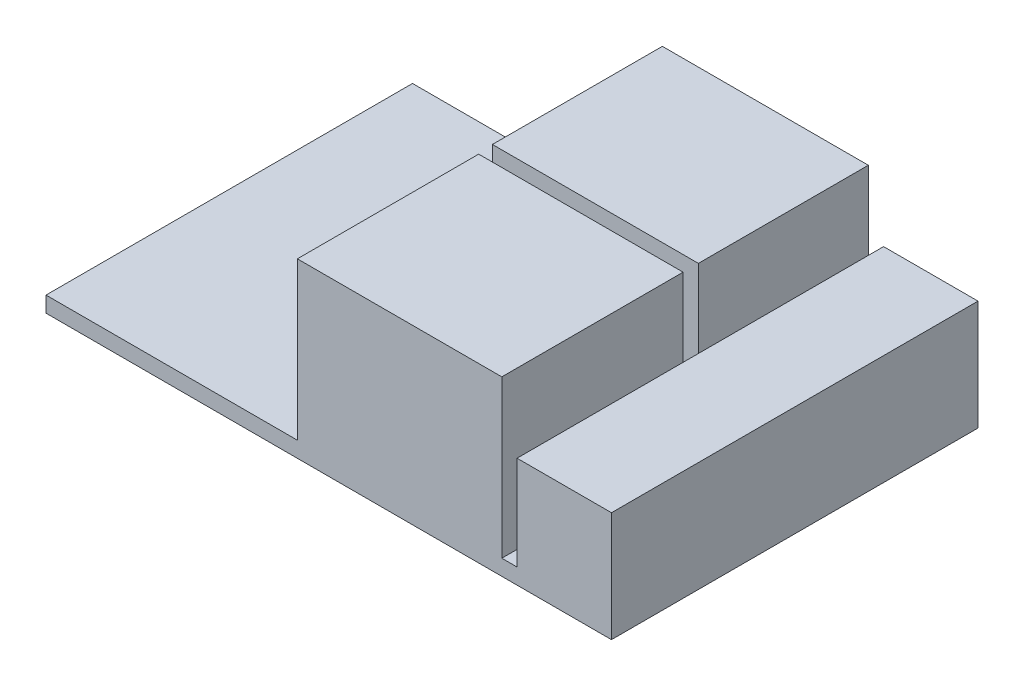
SolidWorks part; units mm, degrees
ref_plane "前视基准面" through (0, 0, 0) normal (0, 0, 1) x (1, 0, 0)
ref_plane "上视基准面" through (0, 0, 0) normal (0, 1, 0) x (1, 0, 0)
ref_plane "右视基准面" through (0, 0, 0) normal (1, 0, 0) x (0, 0, -1)
other "Configuration Table"
sketch "草图1" plane through (0, 0, 0) normal (0, 1, 0) x (1, 0, 0)
  line L0 (203.5758, 850.9118) -> (1017.879, 850.9118) construction
  line L3 (0, 137.1079) -> (54, 137.1079)
  line L4 (0, 137.1079) -> (0, 102.1079)
  line L5 (0, 102.1079) -> (54, 102.1079)
  line L6 (54, 137.1079) -> (54, 102.1079)
  line L7 (54, 137.1079) -> (47.2787, 137.1079)
  line L8 (54, 137.1079) -> (54, 102.1079)
  line L9 (54, 102.1079) -> (47.2787, 102.1079)
  line L10 (47.2787, 137.1079) -> (47.2787, 102.1079) construction
  line L11 (54, 137.1079) -> (47.2787, 102.1079) construction
  line L12 (54, 102.1079) -> (47.2787, 137.1079) construction
  line L13 (23.802, 137.1079) -> (45.2592, 137.1079)
  line L14 (23.802, 137.1079) -> (23.802, 119.6079) construction
  line L15 (23.802, 119.6079) -> (45.2592, 119.6079) construction
  line L16 (45.2592, 137.1079) -> (45.2592, 119.6079) construction
  line L17 (23.802, 137.1079) -> (45.2592, 119.6079) construction
  line L18 (23.802, 119.6079) -> (45.2592, 137.1079) construction
  line L19 (23.802, 118.4725) -> (45.2592, 118.4725) construction
  line L20 (23.802, 118.4725) -> (23.802, 102.1079) construction
  line L21 (23.802, 102.1079) -> (45.2592, 102.1079)
  line L22 (45.2592, 118.4725) -> (45.2592, 102.1079) construction
  line L23 (23.802, 118.4725) -> (45.2592, 102.1079) construction
  line L24 (23.802, 102.1079) -> (45.2592, 118.4725) construction
  point P9 (50.6394, 119.6079)
  point P14 (34.5306, 128.3579)
  point P19 (34.5306, 110.2902)
  dimension "D1" = 35
  dimension "D2" = 54
  dimension "D3" = 0
extrude "凸台-拉伸1" add sketch "草图1" along normal blind 1.5 contours L6 L3 L4 L5 region at (27, 0, -119.6079)
sketch "草图2" plane through (0, 1.5, 0) normal (0, 1, 0) x (1, 0, 0)
  line L0 (0, 102.1079) -> (54, 102.1079) construction
  line L1 (54, 137.1079) -> (44.9839, 137.1079)
  line L2 (54, 137.1079) -> (54, 102.1079)
  line L3 (54, 102.1079) -> (44.9839, 102.1079)
  line L4 (44.9839, 137.1079) -> (44.9839, 102.1079)
  line L5 (54, 137.1079) -> (44.9839, 102.1079) construction
  line L6 (54, 102.1079) -> (44.9839, 137.1079) construction
  line L7 (0, 137.1079) -> (54, 137.1079) construction
  line L8 (23.8587, 137.1079) -> (43.527, 137.1079)
  line L9 (23.8587, 137.1079) -> (23.8587, 120.8778)
  line L10 (23.8587, 120.8778) -> (43.527, 120.8778)
  line L11 (43.527, 137.1079) -> (43.527, 120.8778)
  line L12 (23.8587, 137.1079) -> (43.527, 120.8778) construction
  line L13 (23.8587, 120.8778) -> (43.527, 137.1079) construction
  line L15 (24.0044, 119.4209) -> (43.527, 119.4209)
  line L16 (24.0044, 119.4209) -> (24.0044, 102.1079)
  line L17 (24.0044, 102.1079) -> (43.527, 102.1079)
  line L18 (43.527, 119.4209) -> (43.527, 102.1079)
  line L19 (24.0044, 119.4209) -> (43.527, 102.1079) construction
  line L20 (24.0044, 102.1079) -> (43.527, 119.4209) construction
  point P4 (49.492, 119.6079)
  point P12 (33.6928, 128.9929)
  point P19 (33.7657, 110.7644)
extrude "凸台-拉伸2" add sketch "草图2" along normal blind 9
sketch "草图3" plane through (0, 10.5, 0) normal (0, 1, 0) x (1, 0, 0)
  line L1 (23.8587, 137.1079) -> (43.527, 137.1079)
  line L2 (23.8587, 137.1079) -> (23.8587, 120.8778)
  line L3 (23.8587, 120.8778) -> (43.527, 120.8778)
  line L4 (43.527, 137.1079) -> (43.527, 120.8778)
  line L5 (23.8587, 137.1079) -> (43.527, 120.8778) construction
  line L6 (23.8587, 120.8778) -> (43.527, 137.1079) construction
  line L7 (43.527, 119.4209) -> (24.0044, 119.4209)
  line L8 (43.527, 119.4209) -> (43.527, 102.1079)
  line L9 (43.527, 102.1079) -> (24.0044, 102.1079)
  line L10 (24.0044, 119.4209) -> (24.0044, 102.1079)
  line L11 (43.527, 119.4209) -> (24.0044, 102.1079) construction
  line L12 (43.527, 102.1079) -> (24.0044, 119.4209) construction
  point P4 (33.6928, 128.9929)
  point P11 (33.7657, 110.7644)
extrude "凸台-拉伸3" add sketch "草图3" along normal blind 6
